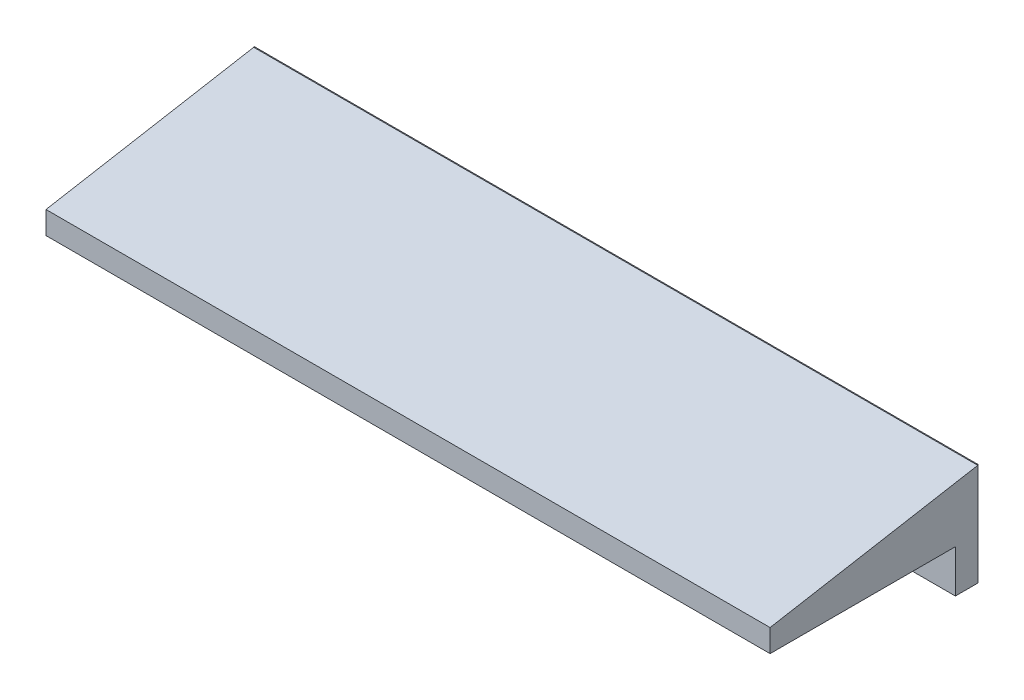
SolidWorks part; units mm, degrees
ref_plane "Front" through (0, 0, 0) normal (0, 0, 1) x (1, 0, 0)
ref_plane "Top" through (0, 0, 0) normal (0, 1, 0) x (1, 0, 0)
ref_plane "Right" through (0, 0, 0) normal (1, 0, 0) x (0, 0, -1)
sketch "Sketch1" plane through (0, 0, 0) normal (0, 1, 0) x (1, 0, 0)
  line L1 (-50.8, -13) -> (50.8, -13)
  line L2 (-50.8, -13) -> (-50.8, 13)
  line L3 (-50.8, 13) -> (50.8, 13)
  line L4 (50.8, -13) -> (50.8, 13)
  line L5 (-50.8, -13) -> (50.8, 13) construction
  line L6 (-50.8, 13) -> (50.8, -13) construction
  point P0 (0, 0)
  dimension "D1" = 26
  dimension "D2" = 101.6
extrude "Boss-Extrude1" add sketch "Sketch1" along normal blind 3.175
sketch "Sketch2" plane through (0, 0, -13) normal (0, 0, -1) x (-1, 0, 0)
  line L0 (50.8, 3.175) -> (-50.8, 3.175)
  line L1 (50.8, 3.175) -> (50.8, -6)
  line L2 (-50.8, 3.175) -> (-50.8, -6)
  line L3 (50.8, -6) -> (-50.8, -6)
  dimension "D1" = 9.175
extrude "Boss-Extrude2" add sketch "Sketch2" along normal blind 3.175
sketch "Sketch3" plane through (0, 0, -13) normal (0, 0, 1) x (1, 0, 0)
  line L0 (50.8, -3) -> (-50.8, -3)
  line L1 (50.8, 0) -> (50.8, -6) construction
  line L2 (-50.8, -6) -> (-50.8, 0) construction
  circle A0 centre (30.3075, -3) radius 1.6
  circle A1 centre (-30.3075, -3) radius 1.6
  circle A2 centre (43.9685, -3) radius 1.6
  circle A3 centre (-43.9685, -3) radius 1.6
  point P10 (0, -3)
  dimension "D3" = 13.661
  dimension "D1" = 30.3075
  dimension "D2" = 30.3075
  dimension "D4" = 13.661
extrude "Cut-Extrude1" cut sketch "Sketch3" against normal blind 3.175 contours A3 | A1 | A2 | A0
sketch "Sketch4" plane through (50.8, 0, 0) normal (1, 0, 0) x (0, 0, -1)
  line L0 (-13, 3.175) -> (16.1432, 8.3137)
  line L1 (-13, 3.175) -> (16.175, 3.175) construction
  line L2 (16.175, 3.175) -> (16.175, 8.4128)
  line L3 (16.175, 3.175) -> (-13, 3.175)
  line L4 (16.175, 8.4128) -> (16.1432, 8.3137)
  line L9 (-13, 0) -> (13, 0)
  line L10 (13, 0) -> (13, -6)
  line L11 (13, -6) -> (16.175, -6)
  line L12 (16.175, -6) -> (16.175, 3.175)
  line L13 (16.175, 3.175) -> (-13, 3.175)
  line L14 (-13, 3.175) -> (-13, 0)
  line L15 (-13, 0) -> (13, 0)
  line L16 (13, 0) -> (13, -6)
  line L17 (13, -6) -> (16.175, -6)
  line L18 (16.175, -6) -> (16.175, 3.175)
  line L20 (-13, 3.175) -> (-13, 0)
  line M6 (16.175, 3.175) -> (-13, 3.175)
  dimension "D1" = 10
  dimension "D2" = 0
extrude "Boss-Extrude3" add sketch "Sketch4" against normal blind 101.6 contours L2 L4 L0 M6 region at (50.8, 4.8898, -6.4502)
